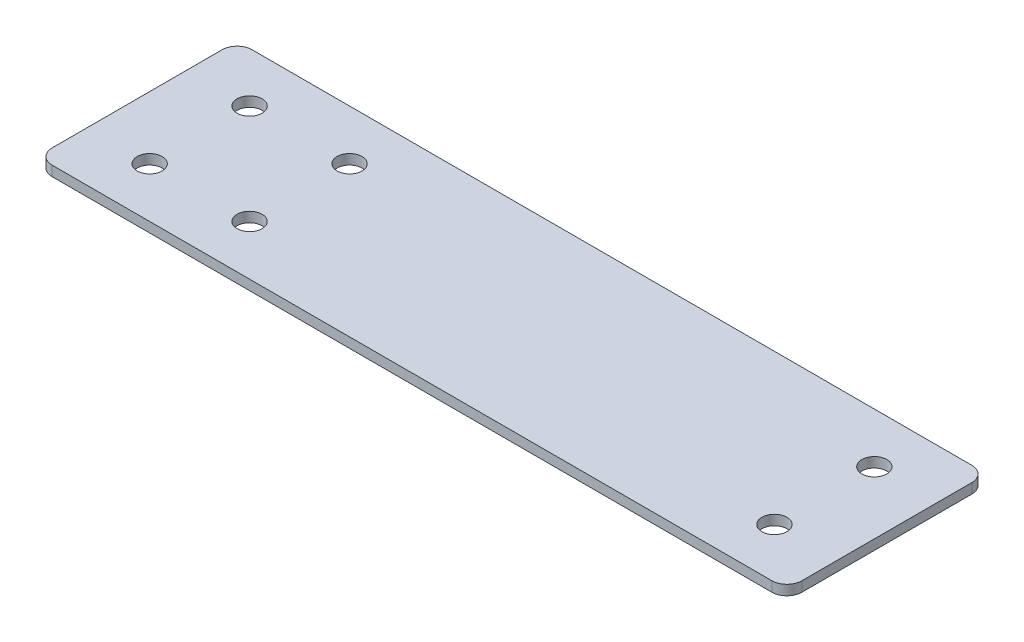
SolidWorks part; units mm, degrees
ref_plane "Front Plane" through (0, 0, 0) normal (0, 0, 1) x (1, 0, 0)
ref_plane "Top Plane" through (0, 0, 0) normal (0, 1, 0) x (1, 0, 0)
ref_plane "Right Plane" through (0, 0, 0) normal (1, 0, 0) x (0, 0, -1)
sketch "Sketch1" plane through (0, 0, 0) normal (0, 1, 0) x (1, 0, 0)
  line L1 (72, -20) -> (-72, -20)
  line L2 (75, -17) -> (75, 17)
  line L3 (72, 20) -> (-72, 20)
  line L4 (-75, -17) -> (-75, 17)
  line L5 (75, -20) -> (-75, 20) construction
  line L6 (75, 20) -> (-75, -20) construction
  arc A0 (-72, -20) -> (-75, -17) centre (-72, -17) cw
  arc A1 (75, 17) -> (72, 20) centre (72, 17) ccw
  arc A2 (72, -20) -> (75, -17) centre (72, -17) ccw
  arc A3 (-72, 20) -> (-75, 17) centre (-72, 17) ccw
  point P0 (0, 0)
  dimension "D3" = 3
  dimension "D1" = 40
  dimension "D2" = 150
base flange "Base-Flange1" sketch "Sketch1" thickness 2 reverse thickness direction yes parameters "D1"=9
sketch "Sketch8" plane through (0, 2, 0) normal (0, 1, 0) x (1, 0, 0)
  line L0 (-75, 17) -> (-75, -17) construction
  line L1 (-72, -20) -> (72, -20) construction
  line L2 (75, -17) -> (75, 17) construction
  point P0 (-62.5, 10)
  point P2 (-62.5, -10)
  point P4 (-42.5, -10)
  point P6 (-42.5, 10)
  point P8 (62.5, 10)
  point P10 (62.5, -10)
  dimension "D1" = 12.5
  dimension "D2" = 10
  dimension "D3" = 20
  dimension "D4" = 12.5
  dimension "D5" = 20
hole_wizard "Ø5.0mm Dowel Hole1" positions "Sketch8" profile "Sketch7" hole size "Ø5.0" standard "ISO" end condition through all
sketch "Sketch7" plane through (-62.5, 2, -10) normal (1, 0, 0) x (0, 0, 1)
  line L0 (0, 0) -> (0, 2)
  line L1 (0, 2) -> (2.5, 2)
  line L2 (2.5, 2) -> (2.5, 0)
  line L5 (2.5, 0) -> (0, 0)
  line L11 (0, -6.35) -> (0, 107.95) construction
  dimension "Thru Hole Dia." = 5
  dimension "Thru Hole Depth" = 2
sketch "Bend-Lines1" [suppressed] plane through (0, 0, 0) normal (0, 1, 0) x (1, 0, 0)
sketch "Bounding-Box1" [suppressed] plane through (0, 0, 0) normal (0, 1, 0) x (1, 0, 0)
sheet metal parameters "Sheet-Metal1" thickness 2 parameters "D1"=9
flat pattern "Flat-Pattern1" [suppressed]
sketch "Bend-Lines2" plane through (0, 0, 0) normal (0, 1, 0) x (1, 0, 0)
sketch3d "Bounding-Box2" [suppressed]
  line L0 (147, 37, 0) -> (-3, 37, 0) construction
  line L1 (147, -3, 0) -> (-3, -3, 0) construction
  line L2 (147, 37, 0) -> (147, -3, 0) construction
  line L3 (-3, 37, 0) -> (-3, -3, 0) construction
sheet metal parameters "Sheet-Metal2" thickness 2 parameters "D1"=9
flat pattern "Flat-Pattern1"
sketch "Bend-Lines2" plane through (0, 0, 0) normal (0, 1, 0) x (1, 0, 0)
sketch3d "Bounding-Box2" [suppressed]
  line L0 (-147, 37, 0) -> (3, 37, 0) construction
  line L1 (-147, -3, 0) -> (3, -3, 0) construction
  line L2 (-147, 37, 0) -> (-147, -3, 0) construction
  line L3 (3, 37, 0) -> (3, -3, 0) construction
